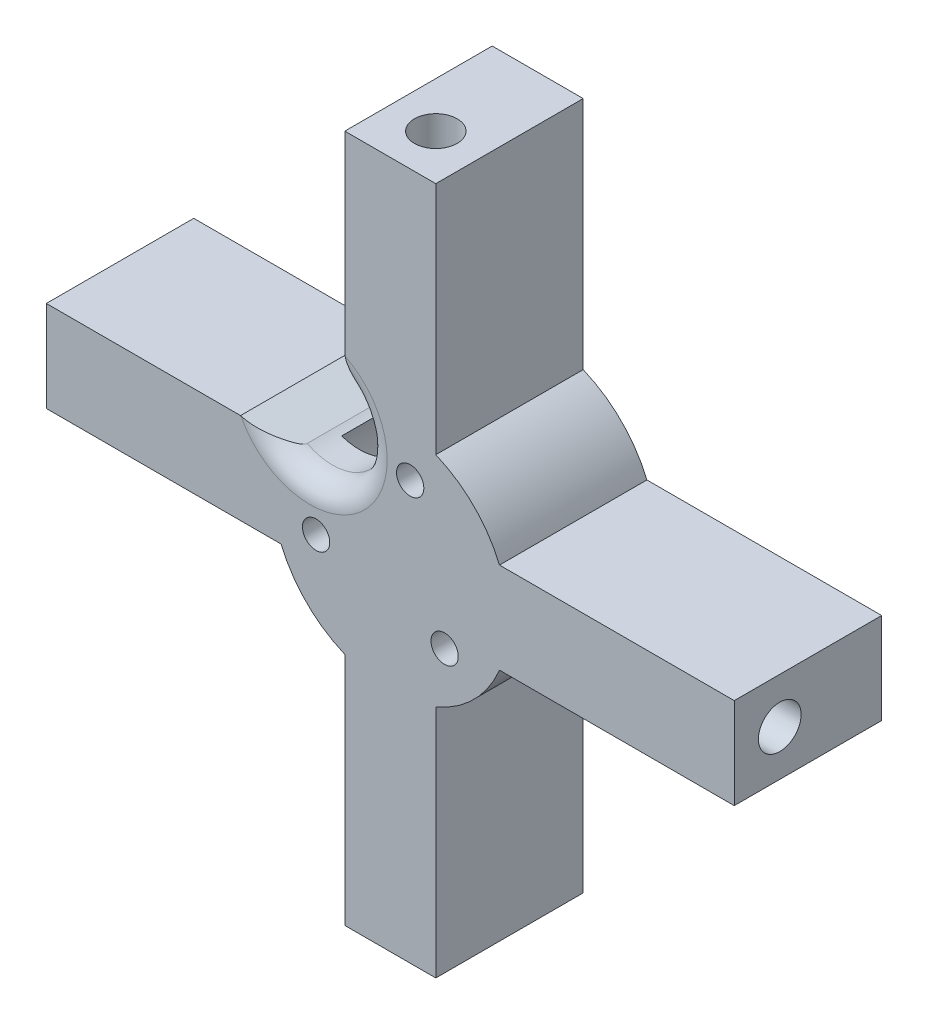
SolidWorks part; units mm, degrees
ref_plane "Front Plane" through (0, 0, 0) normal (0, 0, 1) x (1, 0, 0)
ref_plane "Top Plane" through (0, 0, 0) normal (0, 1, 0) x (1, 0, 0)
ref_plane "Right Plane" through (0, 0, 0) normal (1, 0, 0) x (0, 0, -1)
sketch "Sketch4" plane through (0, 0, 0) normal (0, 0, 1) x (1, 0, 0)
  line L12 (-5, 37.8) -> (5, 37.8)
  line L14 (0, 0) -> (0, 37.8)
  line L15 (-5, 37.8) -> (-5, 12)
  line L16 (5, 37.8) -> (5, 12)
  line L17 (37.8, 5) -> (12, 5)
  line L18 (37.8, 5) -> (37.8, -5)
  line L19 (37.8, -5) -> (12, -5)
  line L20 (5, -37.8) -> (5, -12)
  line L21 (5, -37.8) -> (-5, -37.8)
  line L22 (-5, -37.8) -> (-5, -12)
  line L23 (-37.8, -5) -> (-12, -5)
  line L24 (-37.8, -5) -> (-37.8, 5)
  line L25 (-37.8, 5) -> (-12, 5)
  circle A4 centre (0, 0) radius 13
  point P1 (0, 0)
  point P5 (0, 37.8)
  point P24 (0, 0)
  dimension "D2" = 37.8
  dimension "D3" = 26
  dimension "D1" = 10
  dimension "D4" = 4
extrude "Boss-Extrude1" add sketch "Sketch4" against normal blind 22.7 contours A4 L22 L21 L20 | A4 L19 L18 L17 | A4 L25 L24 L23 | A4 | A4 L14 L12 L15 | A4 L16 L12 L14 region at (-2.5164, 25.2342, 0) region at (2.5164, 25.2342, 0) region at (-2.4774, 12.387, 0) region at (-25.2342, 0, 0) region at (25.2342, 0, 0) region at (0, -25.2342, 0)
sketch "Sketch5" plane through (0, 0, 0) normal (0, 0, 1) x (1, 0, 0)
  line L0 (-5, 16.4565) -> (-3.5231, 11.6214)
  line L1 (-5, 37.8) -> (-5, 12) construction
  line L2 (-8.1541, -2.1849) -> (5.9692, -5.9692) construction
  line L3 (5.9692, -5.9692) -> (2.1849, 8.1541) construction
  line L4 (2.1849, 8.1541) -> (-8.1541, -2.1849) construction
  line L5 (0, 0) -> (2.1849, 8.1541) construction
  line L6 (0, 0) -> (5.9692, -5.9692) construction
  line L7 (0, 0) -> (-8.1541, -2.1849) construction
  line L8 (-8.8388, 8.8388) -> (-8.1541, -2.1849) construction
  line L9 (2.1849, 8.1541) -> (-8.8388, 8.8388) construction
  line L12 (-5, 16.4565) -> (-6.9295, 14.5269)
  line L13 (-37.8, 5) -> (-12, 5) construction
  line L14 (-16.4565, 5) -> (-11.6214, 3.5231)
  line L15 (-14.5269, 6.9295) -> (-16.4565, 5)
  circle A3 centre (0, 0) radius 12.5
  circle A5 centre (2.1849, 8.1541) radius 1.5
  circle A6 centre (-8.1541, -2.1849) radius 1.5
  circle A7 centre (5.9692, -5.9692) radius 1.5
  arc A8 (-6.9295, 14.5269) -> (-14.5269, 6.9295) centre (-8.8388, 8.8388) ccw
  arc A9 (-11.6214, 3.5231) -> (-3.5231, 11.6214) centre (-8.8388, 8.8388) ccw
  point P24 (0, 0)
  dimension "D2" = 3
  dimension "D3" = 8.4418
  dimension "D12" = 12
  dimension "D4" = 2.7288
  dimension "D5" = 5.0556
extrude "Cut-Extrude1" cut sketch "Sketch5" against normal blind 70 contours A8 L15 L14 A9 L0 L12 | A5 | A6 | A7
sketch "Sketch6" plane through (0, 0, -22.7) normal (0, 0, -1) x (-1, 0, 0)
  circle A1 centre (0, 0) radius 11.25
  dimension "D1" = 22.5
extrude "Cut-Extrude3" cut sketch "Sketch6" against normal blind 17.25 and the other way blind 17.25 contours A1
sketch "Sketch7" plane through (0, 0, -5.45) normal (0, 0, -1) x (-1, 0, 0)
  circle A0 centre (-2.1849, 8.1541) radius 2
  circle A3 centre (-5.9692, -5.9692) radius 2
  circle A4 centre (8.1541, -2.1849) radius 2
  dimension "D1" = 4
  dimension "D2" = 4
  dimension "D3" = 4
extrude "Cut-Extrude4" cut sketch "Sketch7" against normal blind 3
sketch "Sketch8" plane through (-5, 0, 0) normal (-1, 0, 0) x (0, 0, 1)
  line L0 (-22.7, 37.8) -> (-16.2, 37.8)
  line L1 (-22.7, 37.8) -> (0, 37.8) construction
  line L2 (-16.2, 37.8) -> (-16.2, -37.8)
  line L3 (-22.7, -37.8) -> (0, -37.8) construction
  line L4 (-16.2, -37.8) -> (-22.7, -37.8)
  line L5 (-22.7, -37.8) -> (-22.7, 37.8)
  dimension "D1" = 6.5
extrude "Cut-Extrude5" cut sketch "Sketch8" against normal blind 66 and the other way blind 58
sketch "Sketch9" plane through (0, 37.8, 0) normal (0, 1, 0) x (1, 0, 0)
  circle A0 centre (0, 5) radius 2.35
  circle A1 centre (0, 5) radius 1.55
  dimension "D2" = 4.7
  dimension "D3" = 3.1
  dimension "D1" = 5
extrude "Cut-Extrude7" cut sketch "Sketch9" against normal blind 4 contours A1 | A0
extrude "Cut-Extrude20" cut sketch "Sketch9<3>" against normal blind 12 contours A1 region at (0, 37.8, -5)
sketch "Sketch9<3>" plane through (0, 37.8, 0) normal (0, 1, 0) x (1, 0, 0) same geometry as "Sketch9"
sketch "Sketch19" plane through (37.8, 0, 0) normal (1, 0, 0) x (0, 0, -1)
  circle A0 centre (5, 0) radius 2.35
  circle A1 centre (5, 0) radius 1.55
  dimension "D1" = 4.7
  dimension "D2" = 3.1
  dimension "D3" = 5
sketch "Sketch20" plane through (0, -37.8, 0) normal (0, -1, 0) x (1, 0, 0)
  circle A0 centre (0, -5) radius 2.35
  circle A1 centre (0, -5) radius 1.55
  dimension "D2" = 3.1
  dimension "D3" = 4.7
  dimension "D1" = 5
sketch "Sketch21" plane through (-37.8, 0, 0) normal (-1, 0, 0) x (0, 0, 1)
  line L0 (-16.2, 0) -> (-5, 0) construction
  line L1 (-16.2, -5) -> (-16.2, 5) construction
  circle A0 centre (-5, 0) radius 1.55
  circle A1 centre (-5, 0) radius 2.35
  dimension "D1" = 3.1
  dimension "D2" = 4.7
extrude "Cut-Extrude22" cut sketch "Sketch21" against normal blind 4
extrude "Cut-Extrude23" cut sketch "Sketch21<2>" against normal blind 12 contours A0 region at (-37.8, 0, -5)
sketch "Sketch21<2>" plane through (-37.8, 0, 0) normal (-1, 0, 0) x (0, 0, 1) same geometry as "Sketch21"
extrude "Cut-Extrude24" cut sketch "Sketch19" against normal blind 4
extrude "Cut-Extrude25" cut sketch "Sketch19<2>" against normal blind 12 contours A1 region at (37.8, 0, -5)
sketch "Sketch19<2>" plane through (37.8, 0, 0) normal (1, 0, 0) x (0, 0, -1) same geometry as "Sketch19"
extrude "Cut-Extrude26" cut sketch "Sketch20" against normal blind 4
extrude "Cut-Extrude27" cut sketch "Sketch20<2>" against normal blind 12 contours A1 region at (0, -37.8, -5)
sketch "Sketch20<2>" plane through (0, -37.8, 0) normal (0, -1, 0) x (1, 0, 0) same geometry as "Sketch20"
fillet "Fillet2" radius 2.5 1 edges at (-4.5962, 4.5962, 0)
sketch "Sketch22" plane through (0, 0, -5.45) normal (0, 0, -1) x (-1, 0, 0)
  line L0 (-11.25, 0) -> (11.25, 0) construction
  arc A0 (3.1667, 10.7951) -> (10.7951, 3.1667) centre (0, 0) ccw construction
  arc A1 (3.1667, 10.7951) -> (10.7951, 3.1667) centre (0, 0) ccw construction
  text T0 "H"
extrude "Boss-Extrude2" add sketch "Sketch22" along normal blind 0.5
